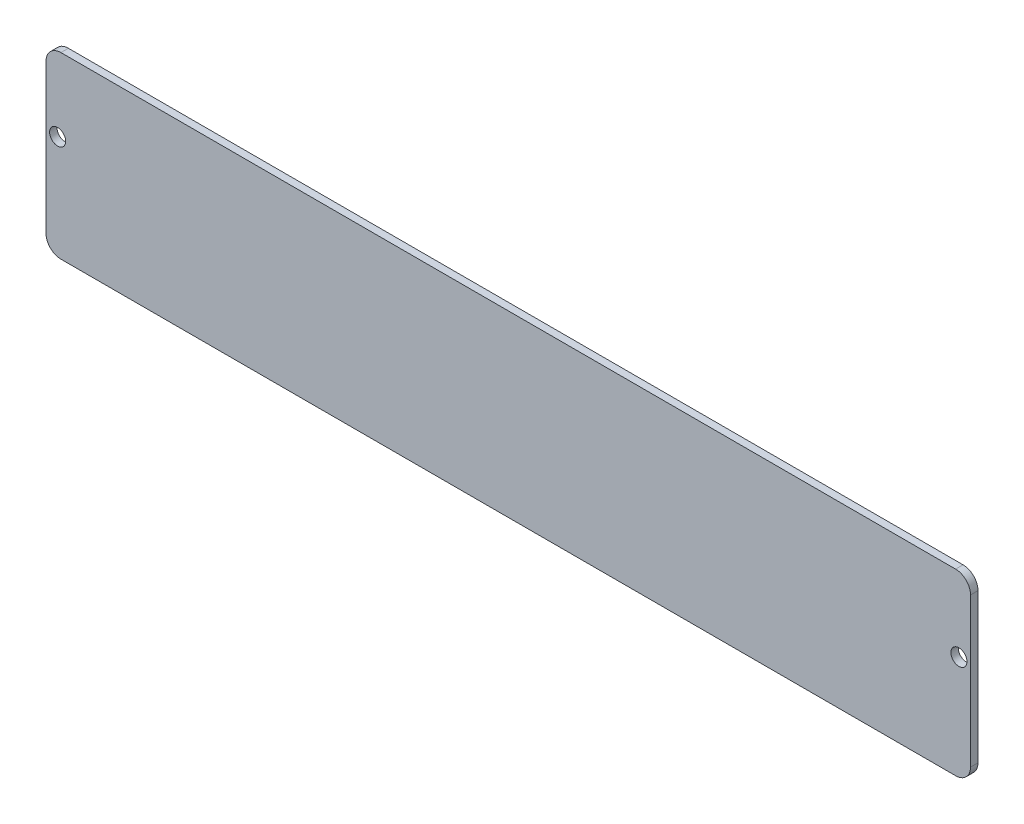
SolidWorks part; units mm, degrees
ref_plane "Front Plane" through (0, 0, 0) normal (0, 0, 1) x (1, 0, 0)
ref_plane "Top Plane" through (0, 0, 0) normal (0, 1, 0) x (1, 0, 0)
ref_plane "Right Plane" through (0, 0, 0) normal (1, 0, 0) x (0, 0, -1)
sketch "Sketch1" plane through (0, 0, 0) normal (0, 0, 1) x (1, 0, 0)
  line L2 (-196.85, 69.85) -> (-196.85, 6.35)
  line L3 (-190.5, 0) -> (190.5, 0)
  line L4 (196.85, 69.85) -> (196.85, 6.35)
  line L5 (-190.5, 76.2) -> (190.5, 76.2)
  line L6 (0, -55) -> (0, 55) construction
  arc A8 (196.85, 69.85) -> (190.5, 76.2) centre (190.5, 69.85) ccw
  arc A9 (-196.85, 69.85) -> (-190.5, 76.2) centre (-190.5, 69.85) cw
  arc A10 (190.5, 0) -> (196.85, 6.35) centre (190.5, 6.35) ccw
  arc A11 (-190.5, 0) -> (-196.85, 6.35) centre (-190.5, 6.35) cw
  circle A12 centre (191.897, 44.45) radius 3.429
  circle A13 centre (-191.897, 44.45) radius 3.429
  point P5 (191.897, 38.8347)
  point P6 (191.897, 37.2569)
  point P11 (196.85, 0)
  point P26 (196.85, 76.2)
  dimension "D3" = 4.953
  dimension "D4" = 6.858
  dimension "D7" = 6.35
  dimension "D1" = 393.7
  dimension "D2" = 76.2
  dimension "D5" = 31.75
extrude "Boss-Extrude1" add sketch "Sketch1" along normal blind 3.175
